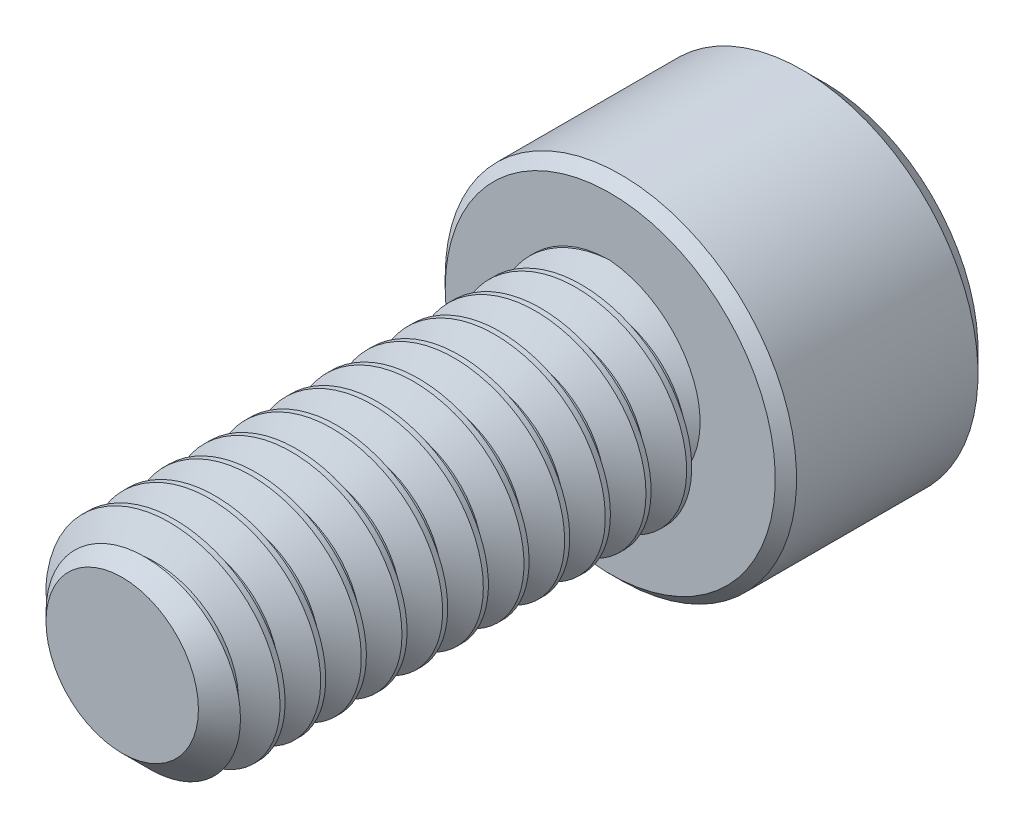
SolidWorks part; units mm, degrees
material "AISI 4340 Steel, normalized"
ref_plane "Front Plane" through (0, 0, 0) normal (0, 0, 1) x (1, 0, 0)
ref_plane "Top Plane" through (0, 0, 0) normal (0, 1, 0) x (1, 0, 0)
ref_plane "Right Plane" through (0, 0, 0) normal (1, 0, 0) x (0, 0, -1)
sketch "Sketch1" plane through (0, 0, 0) normal (0, 0, 1) x (1, 0, 0)
  line L0 (0, 2.0828) -> (0, -2.0828) construction
  circle A0 centre (0, 0) radius 2.0828
  dimension "OD" = 4.1656
extrude "Extrude1" add sketch "Sketch1" against normal blind 9.525
sketch "Sketch2" plane through (0, 0, 0) normal (0, 0, 1) x (1, 0, 0)
  circle A0 centre (0, 0) radius 2.0828 construction
  circle A1 centre (0, 0) radius 2.0828
curve "Helix/Spiral1" pitch 0.7937 height 10.3188 turns 13 parameters "pitch"=0.7937
chamfer "Chamfer3" distance 0.5953 angle 45 1 edges at (2.0828, 0, 0)
sketch "Sketch3" plane through (0, 0, 0) normal (1, 0, 0) x (0, 0, -1)
  line L0 (-0.6945, 2.0828) -> (-0.3969, 1.5672)
  line L1 (-0.3969, 1.5672) -> (-0.2977, 1.5672)
  line L2 (-0.2977, 1.5672) -> (0, 2.0828)
  line L3 (-0.6945, 2.0828) -> (0, 2.0828)
  line L4 (-0.3473, 2.0828) -> (-0.3473, 1.5672) construction
  line L5 (-0.5457, 1.825) -> (-0.1488, 1.825) construction
  line L6 (0, 2.0828) -> (0, -2.0828) construction
  dimension "D1" = 0.0992
  dimension "D2" = 0.3969
  dimension "D3" = 60
sweep "Cut-Sweep1" cut profiles "Sketch3" path "Helix/Spiral1"
sketch "Sketch6" plane through (0, 0, -9.525) normal (0, 0, -1) x (-1, 0, 0)
  circle A0 centre (0, 0) radius 3.429
  dimension "head dia" = 6.858
extrude "Extrude2" add sketch "Sketch6" along normal blind 4.1656
sketch "Sketch7" plane through (0, 0, -13.6906) normal (0, 0, -1) x (-1, 0, 0)
  line L1 (0, 2.0622) -> (-1.7859, 1.0311)
  line L2 (-1.7859, 1.0311) -> (-1.7859, -1.0311)
  line L3 (-1.7859, -1.0311) -> (0, -2.0622)
  line L4 (0, -2.0622) -> (1.7859, -1.0311)
  line L5 (1.7859, -1.0311) -> (1.7859, 1.0311)
  line L6 (1.7859, 1.0311) -> (0, 2.0622)
  circle A0 centre (0, 0) radius 1.7859 construction
  dimension "hex dia" = 3.5719
extrude "Cut-Extrude1" cut sketch "Sketch7" against normal blind 2.6789
sketch "Sketch8" plane through (0, 0, -13.6906) normal (0, 0, -1) x (-1, 0, 0)
  circle A0 centre (0, 0) radius 2.0622
extrude "Cut-Extrude2" cut sketch "Sketch8" against normal blind 0.4166 draft 45
chamfer "Chamfer1" distance 0.4166 angle 45 1 edges at (-3.429, 0, -13.6906)
chamfer "Chamfer2" distance 0.2083 angle 45 1 edges at (-3.429, 0, -9.525)
sketch "Sketch9" plane through (0, 0, 0) normal (1, 0, 0) x (0, 0, -1)
  line L0 (0, 2.0828) -> (0, -2.0828) construction
  line L1 (4.3656, 2.0828) -> (4.3656, -2.0828) construction
  line L2 (9.525, 3.429) -> (9.525, -3.429) construction
  line L3 (13.6906, 3.429) -> (13.6906, -3.429) construction
  line L4 (13.6906, 0) -> (0, 0) construction
  dimension "D1" = 4.3656
  dimension "D2" = 4.1656
  dimension "D3" = 6.858
  dimension "D4" = 9.525
equation "\"D3@Helix/Spiral1\" = \"screw length@Extrude1\"+\"pitch@Helix/Spiral1\""
equation "\"D1@Sketch3\" = \"pitch@Helix/Spiral1\"*.125"
equation "\"D2@Sketch3\" = \"pitch@Helix/Spiral1\"*.5"
equation "\"D1@Cut-Extrude1\" = \"hex dia@Sketch7\"*.75"
equation "\"D1@Chamfer1\" = \"head depth@Extrude2\"/10"
equation "\"D1@Sketch9\" = \"pitch@Helix/Spiral1\"*5.5"
equation "\"D1@Chamfer2\" = \"D1@Chamfer1\"/2"
equation "\"D1@Cut-Extrude2\" = \"D1@Chamfer2\"*2"
equation "\"D1@Chamfer3\" = \"pitch@Helix/Spiral1\"*.750"
equation "\"D2@Sketch9\" = \"head depth@Extrude2\""
equation "\"D3@Sketch9\" = \"head dia@Sketch6\""
equation "\"D4@Sketch9\" = \"screw length@Extrude1\""
